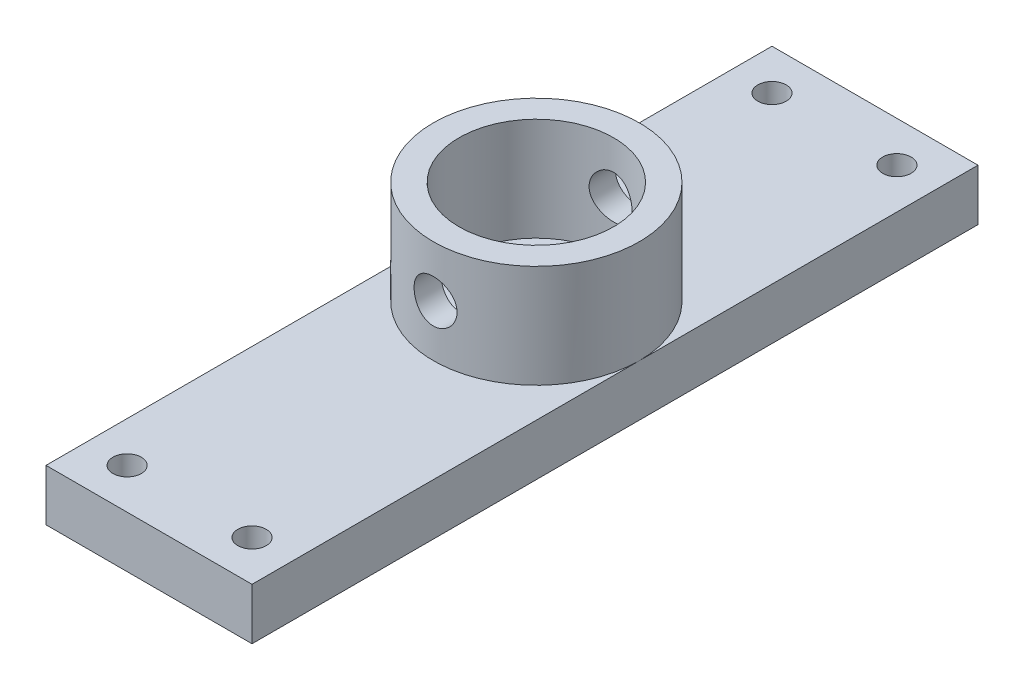
SolidWorks part; units mm, degrees
ref_plane "Front Plane" through (0, 0, 0) normal (0, 0, 1) x (1, 0, 0)
ref_plane "Top Plane" through (0, 0, 0) normal (0, 1, 0) x (1, 0, 0)
ref_plane "Right Plane" through (0, 0, 0) normal (1, 0, 0) x (0, 0, -1)
sketch "Sketch1" plane through (0, 0, 0) normal (0, 1, 0) x (1, 0, 0)
  line L1 (0, 0) -> (25.4, 0)
  line L2 (0, 0) -> (0, 89.5)
  line L3 (0, 89.5) -> (25.4, 89.5)
  line L4 (25.4, 0) -> (25.4, 89.5)
  circle A0 centre (5, 84.5) radius 1.75
  circle A1 centre (20.4, 84.5) radius 1.75
  circle A2 centre (5, 5) radius 1.75
  circle A3 centre (20.4, 5) radius 1.75
  dimension "D3" = 3.5
  dimension "D1" = 89.5
  dimension "D2" = 25.4
  dimension "D4" = 5
  dimension "D5" = 5
  dimension "D6" = 5
  dimension "D7" = 5
extrude "Boss-Extrude1" add sketch "Sketch1" along normal blind 6.35
sketch "Sketch2" plane through (0, 6.35, 0) normal (0, 1, 0) x (1, 0, 0)
  line L1 (25.4, 89.5) -> (0, 89.5) construction
  circle A0 centre (12.7, 47.75) radius 12.7
  circle A1 centre (12.7, 47.75) radius 9.525
  point P2 (12.7, 89.5)
  dimension "D1" = 41.75
  dimension "D2" = 25.4
  dimension "D3" = 19.05
extrude "Boss-Extrude2" add sketch "Sketch2" along normal blind 12.7
sketch "Sketch3" plane through (0, 0, 0) normal (1, 0, 0) x (0, 0, -1)
  line L1 (0, 6.35) -> (0, 0) construction
  line L3 (60.45, 19.05) -> (35.05, 19.05) construction
  circle A0 centre (36.75, 12.7) radius 2.5
  dimension "D1" = 36.75
  dimension "D3" = 5
  dimension "D2" = 6.35
ref_plane "Plane1" through (0, 0, -35.05) normal (0, 0, 1) x (0, -1, 0)
sketch "Sketch4" plane through (0, 0, -35.05) normal (0, 0, 1) x (0, -1, 0)
  line L0 (-6.35, 25.4) -> (-19.05, 25.4) construction
  line L2 (-6.35, 0) -> (-6.35, 25.4) construction
  circle A0 centre (-12.7, 12.7) radius 2.65
  dimension "D1" = 12.7
  dimension "D3" = 5.3
  dimension "D2" = 6.35
extrude "Cut-Extrude2" cut sketch "Sketch4" against normal blind 33.02
